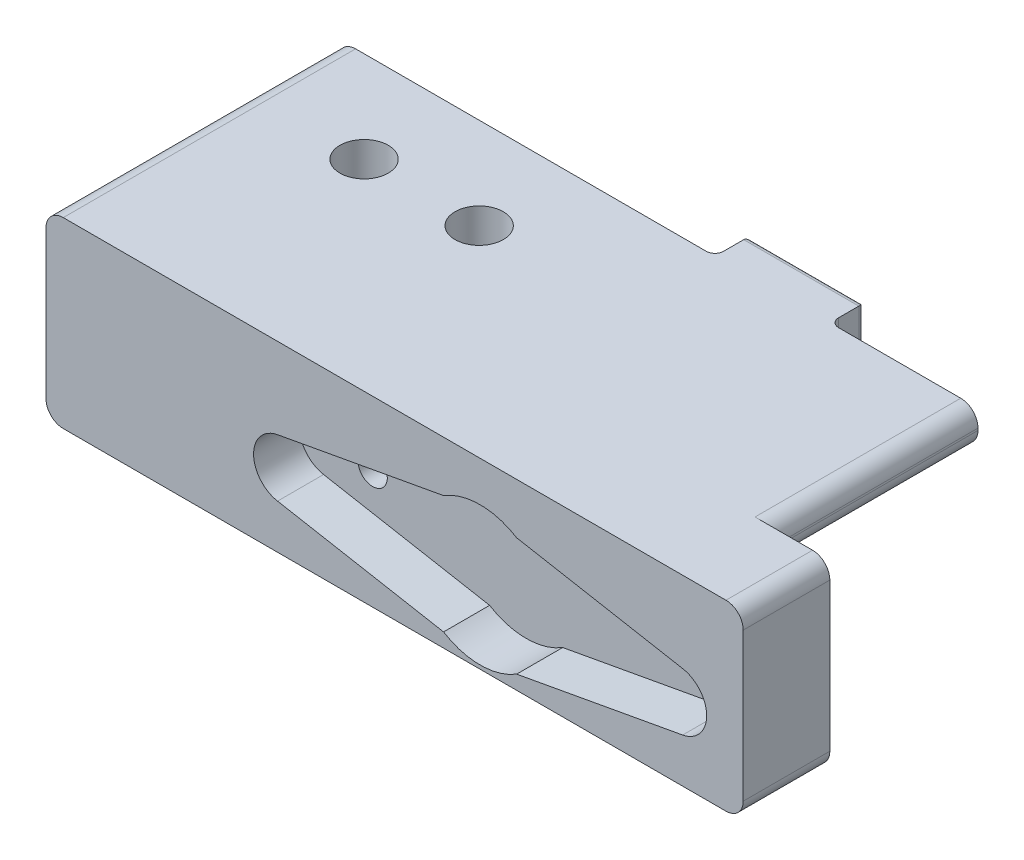
SolidWorks part; units mm, degrees
ref_plane "Front Plane" through (0, 0, 0) normal (0, 0, 1) x (1, 0, 0)
ref_plane "Top Plane" through (0, 0, 0) normal (0, 1, 0) x (1, 0, 0)
ref_plane "Right Plane" through (0, 0, 0) normal (1, 0, 0) x (0, 0, -1)
sketch "Sketch1" plane through (0, 0, 0) normal (0, 0, 1) x (1, 0, 0)
  line L1 (-37.719, -6.35) -> (37.719, -6.35)
  line L2 (-37.719, -6.35) -> (-37.719, 6.35)
  line L3 (-37.719, 6.35) -> (37.719, 6.35)
  line L4 (37.719, -6.35) -> (37.719, 6.35)
  line L5 (0, 6.35) -> (0, -6.35) construction
  line L6 (-37.719, 0) -> (37.719, 0) construction
  point P0 (0, 0)
  dimension "D1" = 75.438
  dimension "D2" = 12.7
extrude "Boss-Extrude1" add sketch "Sketch1" along normal blind 6.35
sketch "Sketch2" plane through (0, 0, 6.35) normal (0, 0, 1) x (1, 0, 0)
  line L1 (0, 0) -> (3.175, 5.1294) construction
  line L2 (0, -1000) -> (0, 49000) construction
  line L3 (3.175, 5.1294) -> (17.6007, 2.4988)
  line L4 (-1000, 0) -> (49000, 0) construction
  line L5 (3.175, -5.1294) -> (17.6007, -2.4988)
  line L6 (-3.175, -5.1294) -> (-17.6007, -2.4988)
  line L7 (-3.175, 5.1294) -> (-17.6007, 2.4988)
  arc A0 (-3.175, -5.1294) -> (3.175, -5.1294) centre (0, 0) ccw
  arc A1 (17.6007, -2.4988) -> (17.6007, 2.4988) centre (17.145, 0) ccw
  arc A2 (-17.6007, -2.4988) -> (-17.6007, 2.4988) centre (-17.145, 0) cw
  arc A3 (3.175, 5.1294) -> (-3.175, 5.1294) centre (0, 0) ccw
  dimension "D1" = 12.065
  dimension "D2" = 5.08
  dimension "D3" = 17.145
  dimension "D4" = 3.175
extrude "Cut-Extrude1" cut sketch "Sketch2" against normal blind 4
sketch "Sketch3" plane through (0, 0, 0) normal (0, 1, 0) x (1, 0, 0)
  line L0 (-34.544, 3.175) -> (34.544, 3.175)
  line L1 (-37.719, 0) -> (37.719, 0)
  line L2 (-37.719, 0) -> (-37.719, 19.05)
  line L3 (-37.719, 19.05) -> (37.719, 19.05)
  line L4 (37.719, 0) -> (37.719, 19.05)
  line L5 (34.544, 3.175) -> (34.544, 15.875)
  line L6 (-34.544, 15.875) -> (34.544, 15.875)
  line L7 (-34.544, 3.175) -> (-34.544, 15.875)
  dimension "D2" = 19.05
  dimension "D1" = 3.175
extrude "Boss-Extrude2" add sketch "Sketch3" along normal up to surface and the other way up to surface up to face at (0, 6.35, 3.175) other way up to face at (0, -6.35, 3.175)
sketch "Sketch4" plane through (0, 6.35, 0) normal (0, 1, 0) x (1, 0, 0)
  line L0 (-37.719, -6.35) -> (-37.719, 19.05) construction
  line L1 (-37.719, -6.35) -> (37.719, -6.35)
  line L2 (-37.719, -6.35) -> (-37.719, 19.05)
  line L3 (-37.719, 19.05) -> (37.719, 19.05)
  line L4 (37.719, -6.35) -> (37.719, 19.05)
extrude "Boss-Extrude4" add sketch "Sketch4" along normal blind 3.175
sketch "Sketch7" plane through (0, 0, 6.35) normal (0, 0, 1) x (1, 0, 0)
  line L0 (-37.719, 9.525) -> (37.719, 9.525) construction
  line L1 (37.719, -6.35) -> (22.86, -6.35)
  line L2 (37.719, -6.35) -> (37.719, 9.525)
  line L3 (37.719, 9.525) -> (22.86, 9.525)
  line L4 (22.86, -6.35) -> (22.86, 9.525)
  arc A0 (17.6007, -2.4988) -> (17.6007, 2.4988) centre (17.145, 0) ccw construction
  point P10 (19.685, 0)
  dimension "D1" = 3.175
extrude "Cut-Extrude3" cut sketch "Sketch7" against normal through all
sketch "Sketch8" plane through (22.86, 0, 0) normal (1, 0, 0) x (0, 0, -1)
  line L1 (15.875, -6.35) -> (19.05, -6.35)
  line L2 (15.875, -6.35) -> (15.875, 9.525)
  line L3 (15.875, 9.525) -> (19.05, 9.525)
  line L4 (19.05, -6.35) -> (19.05, 9.525)
extrude "Cut-Extrude4" cut sketch "Sketch8" against normal through all
sketch "Sketch9" plane through (0, 0, -15.875) normal (0, 0, -1) x (-1, 0, 0)
  line L6 (34.544, 6.35) -> (34.544, -6.35)
  line L7 (34.544, -6.35) -> (37.719, -6.35)
  line L8 (37.719, -6.35) -> (37.719, 9.525)
  line L9 (37.719, 9.525) -> (-22.86, 9.525)
  line L10 (-22.86, 9.525) -> (-22.86, 6.35)
  line L11 (-22.86, 6.35) -> (34.544, 6.35)
  line L12 (34.544, 6.35) -> (34.544, -6.35)
  line L13 (34.544, -6.35) -> (37.719, -6.35)
  line L14 (37.719, -6.35) -> (37.719, 9.525)
  line L15 (37.719, 9.525) -> (-22.86, 9.525)
  line L16 (-22.86, 9.525) -> (-22.86, 6.35)
  line L17 (-22.86, 6.35) -> (34.544, 6.35)
  dimension "D1" = 0
extrude "Boss-Extrude5" add sketch "Sketch9" along normal blind 3.175
sketch "Sketch10" plane through (0, 6.35, 0) normal (0, -1, 0) x (1, 0, 0)
  line L0 (-1034.544, -11.1125) -> (48965.456, -11.1125) construction
  line L1 (-34.544, -3.175) -> (-34.544, -19.05) construction
  line L2 (-1042.3688, -14.9275) -> (48957.6312, -14.9275) construction
  circle A0 centre (-27.544, -11.1125) radius 2.1
  circle A1 centre (-17.544, -11.1125) radius 2.1
  point P9 (-34.544, -11.1125)
  dimension "D3" = 4.2
  dimension "D4" = 4.2
  dimension "D1" = 10
  dimension "D2" = 7
sketch "Sketch11" plane through (0, 0, -3.175) normal (0, 0, -1) x (-1, 0, 0)
  line L1 (-22.86, 6.35) -> (34.544, 6.35)
  line L2 (-22.86, 6.35) -> (-22.86, -6.35)
  line L3 (-22.86, -6.35) -> (34.544, -6.35)
  line L4 (34.544, 6.35) -> (34.544, -6.35)
extrude "Cut-Extrude5" cut sketch "Sketch11" against normal blind 2
sketch "Sketch12" plane through (0, 0, 2.35) normal (0, 0, 1) x (1, 0, 0)
  line L0 (0, -1000) -> (0, 49000) construction
  circle A0 centre (13.335, 0) radius 1.27
  circle A1 centre (-13.335, 0) radius 1.27
  dimension "D1" = 2.54
  dimension "D2" = 13.335
extrude "Cut-Extrude6" cut sketch "Sketch12" against normal through all
extrude "Cut-Extrude7" cut sketch "Sketch10" against normal through all
sketch "Sketch13" plane through (22.86, 0, 0) normal (1, 0, 0) x (0, 0, -1)
  line L1 (1.175, 6.35) -> (19.05, 6.35)
  line L2 (1.175, 6.35) -> (1.175, 9.525)
  line L3 (1.175, 9.525) -> (19.05, 9.525)
  line L4 (19.05, 6.35) -> (19.05, 9.525)
extrude "Cut-Extrude8" cut sketch "Sketch13" against normal blind 5
fillet "Fillet2" radius 1.5 8 edges at (-37.719, 9.525, -6.35) (-34.544, 6.35, -10.1125) (-37.719, -6.35, -6.35) (-34.544, -6.35, -10.1125) (22.86, 9.525, 2.5875) (22.86, -6.35, 2.5875) (17.86, 9.525, -10.1125) (17.86, 6.35, -10.1125)
sketch "Sketch14" plane through (0, 0, -19.05) normal (0, 0, -1) x (-1, 0, 0)
  line L5 (0, -1000) -> (0, 49000) construction
  line L6 (36.219, 9.525) -> (-16.36, 9.525) construction
  line L7 (-5, -5.1301) -> (5, -5.1301)
  line L8 (-5, -5.1301) -> (-5, 9.525)
  line L9 (-5, 9.525) -> (5, 9.525)
  line L10 (5, -5.1301) -> (5, 9.525)
  line L11 (0, 9.525) -> (0, -5.1301) construction
  line L12 (-5, 2.1975) -> (5, 2.1975) construction
  point P1 (0, 2.1975)
  dimension "D1" = 10
extrude "Boss-Extrude6" add sketch "Sketch14" along normal blind 3
sketch "Sketch15" plane through (0, 0, -22.05) normal (0, 0, -1) x (-1, 0, 0)
  circle A0 centre (0, 0) radius 2.123
  dimension "D1" = 4.246
extrude "Cut-Extrude9" cut sketch "Sketch15" against normal blind 2.032
fillet "Fillet3" radius 0.5 6 edges at (-5, -5.1301, -20.55) (5, -5.1301, -20.55) (5, 2.1975, -22.05) (-5, 2.1975, -22.05) (0, -5.1301, -22.05) (0, 9.525, -22.05)
fillet "Fillet4" radius 0.75 1 edges at (5, 7.9375, -19.05) type face fillet first side face at (13.1769, 7.9375, -19.05) second side face at (5, 3.228, -20.05)
fillet "Fillet5" radius 0.75 1 edges at (-5, 7.9375, -19.05) type face fillet first side face at (-5, 3.228, -20.05) second side face at (-29.6673, 2.2225, -19.05)
fillet "Fillet6" radius 0.75 1 edges at (0, 6.35, -19.05) type face fillet first side face at (-3.3368, 6.35, -15.5939) second side face at (0, -1.1712, -19.05)
